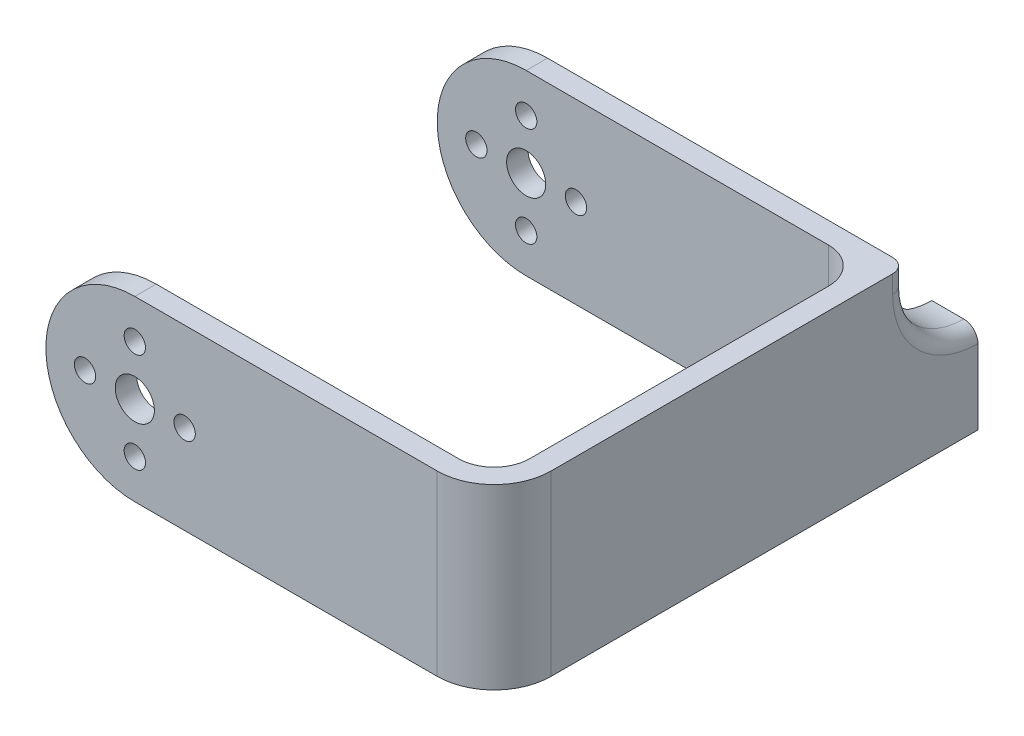
SolidWorks part; units mm, degrees
ref_plane "Plan de face" through (0, 0, 0) normal (0, 0, 1) x (1, 0, 0)
ref_plane "Plan de dessus" through (0, 0, 0) normal (0, 1, 0) x (1, 0, 0)
ref_plane "Plan de droite" through (0, 0, 0) normal (1, 0, 0) x (0, 0, -1)
sketch "Esquisse1" plane through (0, 0, 0) normal (0, 1, 0) x (1, 0, 0)
  line L0 (-3, 21) -> (-3, -21)
  line L5 (-63, 26) -> (-8, 26)
  line L7 (-63, -26) -> (-8, -26)
  line L9 (-63, 26) -> (-8, 26)
  line L10 (-63, 26) -> (-63, 29)
  line L11 (-63, 29) -> (-3, 29)
  line L13 (-63, -26) -> (-8, -26)
  line L14 (-63, -26) -> (-63, -29)
  line L15 (-63, -29) -> (-3, -29)
  line L17 (-3, 29) -> (0, 29)
  line L19 (-3, -29) -> (0, -29)
  line L20 (0, 29) -> (0, -29)
  arc A0 (-8, -26) -> (-3, -21) centre (-8, -21) ccw
  arc A1 (-3, 21) -> (-8, 26) centre (-8, 21) ccw
  point P0 (0, 0)
  point P1 (-3, 0)
  dimension "D9" = 5
  dimension "D1" = 60
  dimension "D2" = 58
  dimension "D3" = 3
  dimension "D4" = 60
  dimension "D5" = 3
  dimension "D6" = 3
  dimension "D7" = 3
  dimension "D8" = 3
extrude "Boss.-Extru.1" add sketch "Esquisse1" along normal blind 12.5 and the other way blind 12.5 contours L20 L17 L11 L10 L5 L0 L7 L14 L15 L19 region at (-3.8589, 0, -25.1411)
sketch "Esquisse2" plane through (0, 0, 29) normal (0, 0, 1) x (1, 0, 0)
  line L0 (-38, 12.5) -> (-38, -12.5) construction
  line L1 (-63, 12.5) -> (0, 12.5) construction
  line L2 (-63, -12.5) -> (0, -12.5) construction
  line L3 (-63, 12.5) -> (-63, -12.5) construction
  line L4 (-63, 12.5) -> (-38, -12.5) construction
  line L5 (-50.5, 12.5) -> (-50.5, -12.5) construction
  line L6 (-50.5, 12.5) -> (-68.7038, 33.6478)
  line L7 (-68.7038, 33.6478) -> (-74.9044, -25.0665)
  line L8 (-74.9044, -25.0665) -> (-54.4069, -18.8459)
  line L9 (-54.4069, -18.8459) -> (-50.5, -12.5)
  line L10 (-50.5, 0) -> (-63, 0) construction
  arc A0 (-50.5, 12.5) -> (-50.5, -12.5) centre (-50.5, 0) ccw
  circle A1 centre (-50.5, 0) radius 2.75
  circle A2 centre (-57.5, 0) radius 1.5
  circle A3 centre (-50.5, 7) radius 1.5
  circle A4 centre (-43.5, 0) radius 1.5
  circle A5 centre (-50.5, -7) radius 1.5
  point P29 (-50.5, 0)
  dimension "D2" = 5.5
  dimension "D4" = 3
  dimension "D1" = 25
  dimension "D3" = 7
  dimension "D5" = 4
extrude "Enlèv. mat.-Extru.2" cut sketch "Esquisse2" against normal through all
sketch "Esquisse3" plane through (0, 0, 0) normal (0, 1, 0) x (1, 0, 0)
  line L1 (-25, 39) -> (0, 39)
  line L2 (-25, 39) -> (-25, 29)
  line L3 (-25, 29) -> (0, 29)
  line L4 (0, 39) -> (0, 29)
  dimension "D1" = 25
  dimension "D2" = 10
extrude "Boss.-Extru.2" add sketch "Esquisse3" against normal blind 12.5
sketch "Esquisse4" plane through (0, 0, 0) normal (0, 1, 0) x (1, 0, 0)
  line L0 (-18.5, 39) -> (-6.5, 44)
  line L1 (-18.5, 35.5359) -> (-18.5, 39)
  line L6 (0, 39) -> (-25, 39) construction
  line L7 (-18.5, 35.5359) -> (-12.5, 32.0718)
  line L12 (-12.5, 32.0718) -> (-6.5, 35.5359)
  line L13 (-18.5, 35.5359) -> (-18.5, 42.4641) construction
  line L14 (-18.5, 42.4641) -> (-12.5, 45.9282) construction
  line L15 (-12.5, 45.9282) -> (-6.5, 42.4641) construction
  line L16 (-6.5, 42.4641) -> (-6.5, 35.5359) construction
  line L17 (-6.5, 35.5359) -> (-6.5, 44)
  point P0 (-18.5, 39)
  point P8 (-12.5, 39)
  dimension "D1" = 120
  dimension "D2" = 120
  dimension "D3" = 12
extrude "Enlèv. mat.-Extru.3" cut sketch "Esquisse4" against normal blind 7.5
fillet "Congé1" radius 8 1 edges at (0, 0, 29)
sketch "Esquisse5" plane through (0, -7.5, 0) normal (0, 1, 0) x (1, 0, 0)
  line L0 (-6.5, 39) -> (-18.5, 39) construction
  circle A0 centre (-12.5, 39) radius 5
  dimension "D1" = 10
extrude "Enlèv. mat.-Extru.4" cut sketch "Esquisse5" against normal through all
sketch "Esquisse6" plane through (0, 0, -39) normal (0, 0, -1) x (-1, 0, 0)
  line L0 (3.25, -3.2) -> (3.25, -9.3) construction
  line L1 (4.85, -3.2) -> (4.85, -9.3)
  line L2 (1.65, -3.2) -> (1.65, -9.3)
  line L3 (3.25, 0) -> (3.25, -12.5) construction
  line L4 (0, 0) -> (6.5, 0) construction
  line L5 (0, -12.5) -> (7.5, -12.5) construction
  line L6 (12.5, -7.5) -> (12.5, 0) construction
  line L7 (21.75, -3.2) -> (21.75, -9.3) construction
  line L8 (20.15, -3.2) -> (20.15, -9.3)
  line L9 (23.35, -3.2) -> (23.35, -9.3)
  arc A0 (4.85, -3.2) -> (1.65, -3.2) centre (3.25, -3.2) ccw
  arc A1 (1.65, -9.3) -> (4.85, -9.3) centre (3.25, -9.3) ccw
  arc A2 (20.15, -3.2) -> (23.35, -3.2) centre (21.75, -3.2) cw
  arc A3 (23.35, -9.3) -> (20.15, -9.3) centre (21.75, -9.3) cw
  point P2 (3.25, -6.25)
  point P16 (3.25, -6.25)
  point P21 (21.75, -6.25)
  dimension "D1" = 1.6
  dimension "D2" = 6.1
extrude "Enlèv. mat.-Extru.5" cut sketch "Esquisse6" against normal blind 4
fillet "Congé2" radius 10 1 edges at (-12.5, 0, -29)
fillet "Congé3" radius 2 3 edges at (-25, 2.9289, -31.9289) (0, 11.25, -29) (0, 2.9289, -31.9289)
